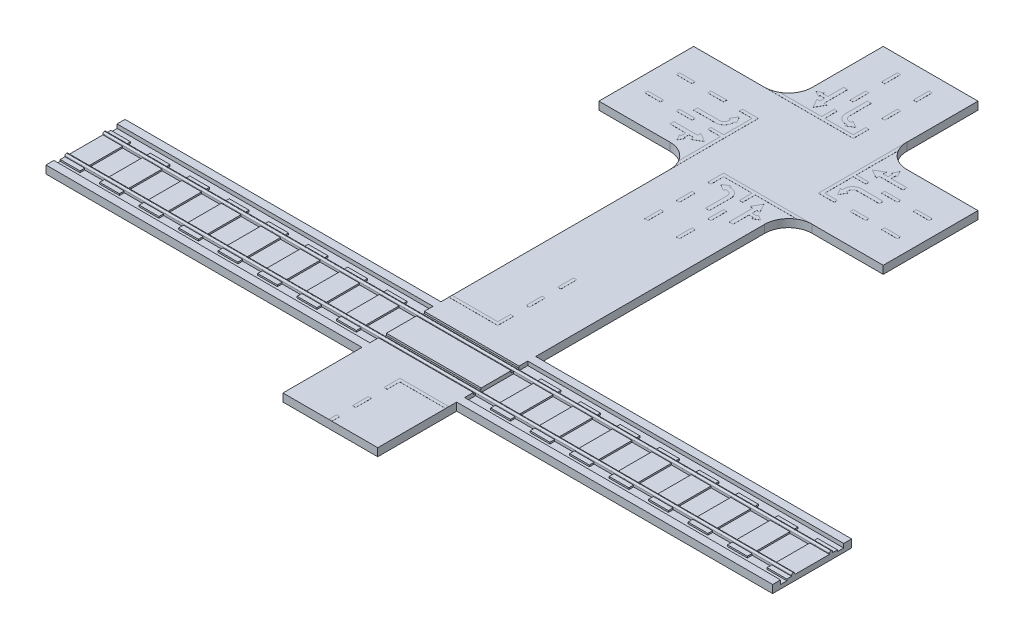
SolidWorks part; units mm, degrees
ref_plane "Front Plane" through (0, 0, 0) normal (0, 0, 1) x (1, 0, 0)
ref_plane "Top Plane" through (0, 0, 0) normal (0, 1, 0) x (1, 0, 0)
ref_plane "Right Plane" through (0, 0, 0) normal (1, 0, 0) x (0, 0, -1)
sketch "Skizze1" plane through (0, 0, 0) normal (0, 1, 0) x (1, 0, 0)
  line L1 (-60, 0) -> (-120, 0)
  line L2 (0, 60) -> (0, 120)
  line L3 (-60, 180) -> (-120, 180)
  line L4 (-180, 60) -> (-180, 120)
  line L7 (-180, 120) -> (-120, 120)
  line L8 (-120, 180) -> (-120, 120)
  line L11 (0, 120) -> (-60, 120)
  line L12 (-60, 180) -> (-60, 120)
  line L15 (0, 60) -> (-60, 60)
  line L16 (-60, 0) -> (-60, 60)
  line L19 (-180, 60) -> (-120, 60)
  line L20 (-120, 0) -> (-120, 60)
  dimension "D3" = 60
  dimension "D4" = 60
  dimension "D5" = 60
  dimension "D6" = 60
  dimension "D7" = 60
  dimension "D8" = 60
  dimension "D9" = 60
  dimension "D10" = 60
extrude "Aufsatz-Linear austragen1" add sketch "Skizze1" along normal blind 5
fillet "Verrundung1" radius 15 4 edges at (-60, 2.5, -120) (-60, 2.5, -60) (-120, 2.5, -60) (-120, 2.5, -120)
sketch "Skizze2" plane through (0, 5, 0) normal (0, 1, 0) x (1, 0, 0)
  line L1 (-101, 60) -> (-99, 60)
  line L2 (-101, 60) -> (-101, 50)
  line L3 (-101, 50) -> (-99, 50)
  line L4 (-99, 60) -> (-99, 50)
  line L5 (-101, 40) -> (-99, 40)
  line L6 (-101, 40) -> (-101, 30)
  line L7 (-101, 30) -> (-99, 30)
  line L8 (-99, 40) -> (-99, 30)
  line L9 (-101, 20) -> (-99, 20)
  line L10 (-101, 20) -> (-101, 10)
  line L11 (-101, 10) -> (-99, 10)
  line L12 (-99, 20) -> (-99, 10)
  line L13 (-120, 0) -> (-60, 0) construction
  line L21 (-120, 45) -> (-120, 0) construction
  line L22 (-81, 20) -> (-81, 10)
  line L23 (-79, 10) -> (-81, 10)
  line L24 (-79, 20) -> (-79, 10)
  line L25 (-79, 20) -> (-81, 20)
  line L26 (-81, 40) -> (-81, 30)
  line L27 (-79, 30) -> (-81, 30)
  line L28 (-79, 40) -> (-79, 30)
  line L29 (-79, 40) -> (-81, 40)
  line L30 (-81, 60) -> (-81, 50)
  line L31 (-79, 50) -> (-81, 50)
  line L32 (-79, 60) -> (-79, 50)
  line L33 (-79, 60) -> (-81, 60)
  line L34 (-60, 79) -> (-60, 81)
  line L35 (-60, 79) -> (-50, 79)
  line L36 (-50, 79) -> (-50, 81)
  line L37 (-60, 81) -> (-50, 81)
  line L38 (-40, 79) -> (-40, 81)
  line L39 (-40, 79) -> (-30, 79)
  line L40 (-30, 79) -> (-30, 81)
  line L41 (-40, 81) -> (-30, 81)
  line L42 (-20, 79) -> (-20, 81)
  line L43 (-20, 79) -> (-10, 79)
  line L44 (-10, 79) -> (-10, 81)
  line L45 (-20, 81) -> (-10, 81)
  line L46 (-20, 99) -> (-10, 99)
  line L47 (-10, 101) -> (-10, 99)
  line L48 (-20, 101) -> (-10, 101)
  line L49 (-20, 101) -> (-20, 99)
  line L50 (-40, 99) -> (-30, 99)
  line L51 (-30, 101) -> (-30, 99)
  line L52 (-40, 101) -> (-30, 101)
  line L53 (-40, 101) -> (-40, 99)
  line L54 (-60, 99) -> (-50, 99)
  line L55 (-50, 101) -> (-50, 99)
  line L56 (-60, 101) -> (-50, 101)
  line L57 (-60, 101) -> (-60, 99)
  line L58 (-120, 101) -> (-120, 99)
  line L59 (-120, 101) -> (-130, 101)
  line L60 (-130, 101) -> (-130, 99)
  line L61 (-120, 99) -> (-130, 99)
  line L62 (-140, 101) -> (-140, 99)
  line L63 (-140, 101) -> (-150, 101)
  line L64 (-150, 101) -> (-150, 99)
  line L65 (-140, 99) -> (-150, 99)
  line L66 (-160, 101) -> (-160, 99)
  line L67 (-160, 101) -> (-170, 101)
  line L68 (-170, 101) -> (-170, 99)
  line L69 (-160, 99) -> (-170, 99)
  line L70 (-160, 81) -> (-170, 81)
  line L71 (-170, 79) -> (-170, 81)
  line L72 (-160, 79) -> (-170, 79)
  line L73 (-160, 79) -> (-160, 81)
  line L74 (-140, 81) -> (-150, 81)
  line L75 (-150, 79) -> (-150, 81)
  line L76 (-140, 79) -> (-150, 79)
  line L77 (-140, 79) -> (-140, 81)
  line L78 (-120, 81) -> (-130, 81)
  line L79 (-130, 79) -> (-130, 81)
  line L80 (-120, 79) -> (-130, 79)
  line L81 (-120, 79) -> (-120, 81)
  line L82 (-79, 120) -> (-81, 120)
  line L83 (-79, 120) -> (-79, 130)
  line L84 (-79, 130) -> (-81, 130)
  line L85 (-81, 120) -> (-81, 130)
  line L86 (-79, 140) -> (-81, 140)
  line L87 (-79, 140) -> (-79, 150)
  line L88 (-79, 150) -> (-81, 150)
  line L89 (-81, 140) -> (-81, 150)
  line L90 (-79, 160) -> (-81, 160)
  line L91 (-79, 160) -> (-79, 170)
  line L92 (-79, 170) -> (-81, 170)
  line L93 (-81, 160) -> (-81, 170)
  line L94 (-99, 160) -> (-99, 170)
  line L95 (-101, 170) -> (-99, 170)
  line L96 (-101, 160) -> (-101, 170)
  line L97 (-101, 160) -> (-99, 160)
  line L98 (-99, 140) -> (-99, 150)
  line L99 (-101, 150) -> (-99, 150)
  line L100 (-101, 140) -> (-101, 150)
  line L101 (-101, 140) -> (-99, 140)
  line L102 (-99, 120) -> (-99, 130)
  line L103 (-101, 130) -> (-99, 130)
  line L104 (-101, 120) -> (-101, 130)
  line L105 (-101, 120) -> (-99, 120)
  dimension "D1" = 2
  dimension "D2" = 2
  dimension "D3" = 2
  dimension "D4" = 10
  dimension "D5" = 10
  dimension "D6" = 10
  dimension "D7" = 10
  dimension "D8" = 10
  dimension "D9" = 10
  dimension "D10" = 19
  dimension "D11" = 19
  dimension "D12" = 19
extrude "Aufsatz-Linear austragen2" add sketch "Skizze2" along normal blind 0.05
sketch "Skizze3" plane through (0, 5, 0) normal (0, 1, 0) x (1, 0, 0)
  line L0 (-72.5, 35) -> (-70, 35)
  line L1 (-70, 35) -> (-70, 45)
  line L2 (-70, 50) -> (-68, 50)
  line L3 (-68, 50) -> (-71.25, 55.6292)
  line L4 (-71.25, 55.6292) -> (-74.5, 50)
  line L5 (-74.5, 50) -> (-72.5, 50)
  line L6 (-72.5, 50) -> (-72.5, 35)
  line L7 (-120, 0) -> (-60, 0) construction
  line L8 (-60, 0) -> (-60, 45) construction
  line L9 (-70, 45) -> (-67, 45)
  line L10 (-67, 45) -> (-67, 44)
  line L11 (-67, 44) -> (-63.5359, 46)
  line L12 (-63.5359, 46) -> (-67, 48)
  line L13 (-67, 48) -> (-67, 47)
  line L14 (-67, 47) -> (-70, 47)
  line L15 (-70, 47) -> (-70, 50)
  line L16 (-81, 58) -> (-52.4833, 58)
  line L17 (-81, 60) -> (-41, 60)
  line L18 (-81, 60) -> (-81, 58)
  line L19 (-81, 58) -> (-52.4833, 58)
  arc A0 (-45, 60) -> (-60, 45) centre (-45, 45) ccw construction
  arc A2 (-45, 60) -> (-52.4833, 58) centre (-45, 45) ccw
  dimension "D1" = 2.5
  dimension "D2" = 1.25
  dimension "D3" = 15
  dimension "D4" = 2
  dimension "D5" = 60
  dimension "D6" = 60
  dimension "D7" = 15
  dimension "D8" = 35
  dimension "D9" = 10
  dimension "D10" = 2
  dimension "D11" = 60
  dimension "D12" = 60
  dimension "D13" = 1
  dimension "D14" = 3
  dimension "D15" = 10
  dimension "D16" = 1
  dimension "D17" = 1
extrude "Aufsatz-Linear austragen8" add sketch "Skizze3" along normal blind 0.05 contours A2 L17 L18 L16 | L14 L15 L2 L3 L4 L5 L6 L0 L1 L9 L10 L11 L12 L13 region at (-70.465, 5, -45.6545) region at (-65.4801, 5, -59.0319)
sketch "Skizze4" plane through (0, 5, 0) normal (0, 1, 0) x (1, 0, 0)
  line L0 (-85, 48.63) -> (-85, 35)
  line L1 (-101, 60) -> (-79, 60)
  line L2 (-101, 60) -> (-101, 58)
  line L3 (-101, 58) -> (-79, 58)
  line L4 (-79, 60) -> (-79, 58)
  line L5 (-85, 35) -> (-87.5, 35)
  line L6 (-87.5, 48.63) -> (-87.5, 35)
  line L7 (-90.5, 51.63) -> (-91.5, 51.63)
  line L8 (-91.5, 51.63) -> (-91.5, 50.38)
  line L9 (-91.5, 50.38) -> (-95.8301, 52.88)
  line L10 (-95.8301, 52.88) -> (-91.5, 55.38)
  line L11 (-91.5, 55.38) -> (-91.5, 54.13)
  line L12 (-90.5, 54.13) -> (-91.5, 54.13)
  line L13 (-120, 0) -> (-60, 0) construction
  line L15 (-81, 60) -> (-81, 50) construction
  line L71 (-101, 60) -> (-101, 58)
  line L72 (-79, 58) -> (-101, 58)
  line L73 (-79, 60) -> (-79, 58)
  line L74 (-79, 60) -> (-101, 60)
  arc A0 (-85, 48.63) -> (-90.5, 54.13) centre (-90.5, 48.63) ccw
  arc A1 (-87.5, 48.63) -> (-90.5, 51.63) centre (-90.5, 48.63) ccw
  dimension "D1" = 2.5
  dimension "D2" = 11
  dimension "D13" = 1
  dimension "D14" = 13.63
  dimension "D12" = 3
  dimension "D3" = 1.25
  dimension "D4" = 1.25
  dimension "D5" = 1.25
  dimension "D6" = 60
  dimension "D7" = 60
  dimension "D8" = 48.63
  dimension "D9" = 0
  dimension "D10" = 35
  dimension "D11" = 9.5
extrude "Aufsatz-Linear austragen13" add sketch "Skizze4" along normal blind 0.05 contours A1 L6 L5 L0 A0 L12 L11 L10 L9 L8 L7 | L4 L1 L2 L3 region at (-85.2308, 5, -41.815) region at (-90, 5, -59)
sketch "Skizze8" plane through (0, 5, 0) normal (0, 1, 0) x (1, 0, 0)
  line L0 (-60, 79) -> (-60, 135)
  line L1 (-60, 135) -> (-60, 79)
  line L2 (-58, 79) -> (-58, 127.5167)
  line L3 (-60, 79) -> (-50, 79) construction
  line L4 (-79, 120) -> (-135, 120)
  line L6 (-135, 120) -> (-79, 120)
  line L7 (-60, 135) -> (-58, 127.5167)
  line L8 (-79, 122) -> (-122, 122)
  line L9 (-79, 120) -> (-79, 130) construction
  line L10 (-79, 122) -> (-79, 120)
  line L11 (-120, 101) -> (-122, 101)
  line L12 (-58, 79) -> (-60, 79)
  line L13 (-108.737, 124.3934) -> (-108.763, 124.3934)
  line L14 (-35, 107.5) -> (-50, 107.5)
  line L15 (-50, 107.5) -> (-50, 105.5)
  line L16 (-50, 105.5) -> (-55.6292, 108.75)
  line L17 (-55.6292, 108.75) -> (-50, 112)
  line L18 (-50, 112) -> (-50, 110)
  line L19 (-50, 110) -> (-47, 110)
  line L20 (-47, 110) -> (-47, 113)
  line L21 (-47, 113) -> (-48, 113)
  line L22 (-48, 113) -> (-46, 116.4641)
  line L23 (-46, 116.4641) -> (-44, 113)
  line L24 (-44, 113) -> (-45, 113)
  line L25 (-45, 113) -> (-45, 110)
  line L26 (-45, 110) -> (-35, 110)
  line L27 (-35, 110) -> (-35, 107.5)
  line L28 (-48.8792, 95) -> (-35, 95)
  line L29 (-35, 95) -> (-35, 92.5)
  line L30 (-35, 92.5) -> (-48.8792, 92.5)
  line L31 (-51.8792, 89.5) -> (-51.8792, 88.5)
  line L32 (-51.8792, 88.5) -> (-50.6292, 88.5)
  line L33 (-50.6292, 88.5) -> (-53.1292, 84.1699)
  line L34 (-53.1292, 84.1699) -> (-55.6292, 88.5)
  line L35 (-55.6292, 88.5) -> (-54.3792, 88.5)
  line L36 (-54.3792, 88.5) -> (-54.3792, 89.5)
  line L37 (-60, 99) -> (-50, 99) construction
  line L38 (0, 60) -> (0, 120) construction
  line L39 (0, 120) -> (-45, 120) construction
  line L40 (-180, 120) -> (-180, 60) construction
  line L41 (-180, 60) -> (-135, 60) construction
  line L42 (-120, 45) -> (-122, 52.4833)
  line L43 (-135, 120) -> (-127.5167, 122)
  line L44 (-79, 122) -> (-79, 120)
  line L51 (-88.4609, 124.3934) -> (-88.5, 124.3934)
  line L53 (-122, 122) -> (-127.5167, 122)
  line L76 (-79, 120) -> (-135, 120)
  line L77 (-135, 120) -> (-79, 120)
  line L78 (-79, 122) -> (-122, 122)
  line L79 (-107.5, 145) -> (-107.5, 130)
  line L80 (-107.5, 130) -> (-105.5, 130)
  line L81 (-105.5, 130) -> (-108.75, 124.3708)
  line L82 (-108.75, 124.3708) -> (-112, 130)
  line L83 (-112, 130) -> (-110, 130)
  line L84 (-110, 130) -> (-110, 133)
  line L85 (-110, 133) -> (-113, 133)
  line L86 (-113, 133) -> (-113, 132)
  line L87 (-113, 132) -> (-116.4641, 134)
  line L88 (-116.4641, 134) -> (-113, 136)
  line L89 (-113, 136) -> (-113, 135)
  line L90 (-113, 135) -> (-110, 135)
  line L91 (-110, 135) -> (-110, 145)
  line L92 (-110, 145) -> (-107.5, 145)
  line L93 (-95, 131.1208) -> (-95, 145)
  line L94 (-95, 145) -> (-92.5, 145)
  line L95 (-92.5, 145) -> (-92.5, 131.1208)
  line L96 (-89.5, 128.1208) -> (-88.5, 128.1208)
  line L97 (-88.5, 128.1208) -> (-88.5, 129.3708)
  line L98 (-88.5, 129.3708) -> (-84.1699, 126.8708)
  line L99 (-84.1699, 126.8708) -> (-88.5, 124.3708)
  line L100 (-88.5, 124.3708) -> (-88.5, 125.6208)
  line L101 (-88.5, 125.6208) -> (-89.5, 125.6208)
  line L104 (-120, 101) -> (-120, 45)
  line L105 (-120, 45) -> (-120, 101)
  line L106 (-122, 101) -> (-122, 52.4833)
  line L107 (-145, 72.5) -> (-130, 72.5)
  line L108 (-130, 72.5) -> (-130, 74.5)
  line L109 (-130, 74.5) -> (-124.3708, 71.25)
  line L110 (-124.3708, 71.25) -> (-130, 68)
  line L111 (-130, 68) -> (-130, 70)
  line L112 (-130, 70) -> (-133, 70)
  line L113 (-133, 70) -> (-133, 67)
  line L114 (-133, 67) -> (-132, 67)
  line L115 (-132, 67) -> (-134, 63.5359)
  line L116 (-134, 63.5359) -> (-136, 67)
  line L117 (-136, 67) -> (-135, 67)
  line L118 (-135, 67) -> (-135, 70)
  line L119 (-135, 70) -> (-145, 70)
  line L120 (-145, 70) -> (-145, 72.5)
  line L121 (-131.1208, 85) -> (-145, 85)
  line L122 (-145, 85) -> (-145, 87.5)
  line L123 (-145, 87.5) -> (-131.1208, 87.5)
  line L124 (-128.1208, 90.5) -> (-128.1208, 91.5)
  line L125 (-128.1208, 91.5) -> (-129.3708, 91.5)
  line L126 (-129.3708, 91.5) -> (-126.8708, 95.8301)
  line L127 (-126.8708, 95.8301) -> (-124.3708, 91.5)
  line L128 (-124.3708, 91.5) -> (-125.6208, 91.5)
  line L129 (-125.6208, 91.5) -> (-125.6208, 90.5)
  arc A0 (-60, 135) -> (-45, 120) centre (-45, 135) ccw construction
  arc A2 (-48.8792, 92.5) -> (-51.8792, 89.5) centre (-48.8792, 89.5) ccw
  arc A3 (-48.8792, 95) -> (-54.3792, 89.5) centre (-48.8792, 89.5) ccw
  arc A4 (-135, 120) -> (-120, 135) centre (-135, 135) ccw construction
  arc A6 (-120, 45) -> (-122, 52.4833) centre (-135, 45) ccw
  arc A7 (-92.5, 131.1208) -> (-89.5, 128.1208) centre (-89.5, 131.1208) ccw
  arc A8 (-95, 131.1208) -> (-89.5, 125.6208) centre (-89.5, 131.1208) ccw
  arc A9 (-131.1208, 87.5) -> (-128.1208, 90.5) centre (-131.1208, 90.5) ccw
  arc A10 (-131.1208, 85) -> (-125.6208, 90.5) centre (-131.1208, 90.5) ccw
  arc A11 (-58, 127.5167) -> (-60, 135) centre (-45, 135) cw
  arc A14 (-127.5167, 122) -> (-135, 120) centre (-135, 135) cw
  dimension "D5" = 3
  dimension "D6" = 5.5
  dimension "D1" = 2
  dimension "D3" = 2
  dimension "D4" = 2.5
  dimension "D7" = 1
  dimension "D8" = 1.25
  dimension "D9" = 1.25
  dimension "D10" = 60
  dimension "D11" = 60
  dimension "D12" = 9.5
  dimension "D13" = 35
  dimension "D14" = 35
  dimension "D15" = 3
  dimension "D16" = 15
  dimension "D17" = 1
  dimension "D18" = 1
  dimension "D19" = 10
  dimension "D20" = 2
  dimension "D21" = 2.5
  dimension "D22" = 2
  dimension "D23" = 2
  dimension "D24" = 60
  dimension "D25" = 60
  dimension "D26" = 60
  dimension "D27" = 60
  dimension "D28" = 3
  dimension "D29" = 10
  dimension "D30" = 5.6292
  dimension "D31" = 0
  dimension "D32" = 2.5
  dimension "D33" = 4.3301
  dimension "D34" = 2
  dimension "D35" = 35
  dimension "D36" = 2.5
  dimension "D37" = 2
  dimension "D38" = 2
  dimension "D39" = 3
  dimension "D40" = 10
  dimension "D41" = 15
  dimension "D42" = 1
  dimension "D43" = 1
  dimension "D44" = 60
  dimension "D45" = 60
  dimension "D46" = 10
  dimension "D47" = 2
  dimension "D48" = 10
  dimension "D49" = 5
  dimension "D50" = 60
  dimension "D51" = 60
  dimension "D52" = 3
  dimension "D53" = 3
  dimension "D54" = 5.6292
  dimension "D55" = 58
extrude "Aufsatz-Linear austragen14" add sketch "Skizze8" along normal blind 0.05 contours L92 L91 L90 L89 L88 L87 L86 L85 L84 L83 L82 L13 L81 L80 L79 | L53 A14 L4 L10 L8 | L93 A8 L101 L100 L51 L99 L98 L97 L96 A7 L95 L94 | L27 L26 L25 L24 L23 L22 L21 L20 L19 L18 L17 L16 L15 L14 | L2 A11 L0 L12 | L28 A3 L36 L35 L34 L33 L32 L31 A2 L30 L29 | A6 L104 L11 L106 | L121 A10 L129 L128 L127 L126 L125 L124 A9 L123 L122 | L120 L119 L118 L117 L116 L115 L114 L113 L112 L111 L110 L109 L108 L107 region at (-59.0194, 5, -104.5004) region at (-104.5004, 5, -120.9806) region at (-120.9806, 5, -75.4996) region at (-109.535, 5, -134.3455) region at (-45.6545, 5, -109.535) region at (-41.9396, 5, -94.767) region at (-88.4805, 5, -124.6262) region at (-134.3455, 5, -70.465) region at (-138.0604, 5, -85.233)
sketch "Skizze9" plane through (0, 5, 0) normal (0, 1, 0) x (1, 0, 0)
  line L0 (-60, 0) -> (-120, 0)
  line L1 (-320, -100) -> (-320, -150)
  line L2 (-120, -150) -> (-120, -200)
  line L3 (140, -150) -> (140, -100)
  line L4 (-120, -200) -> (-60, -200)
  line L5 (-60, 0) -> (-60, -100)
  line L6 (-60, -100) -> (140, -100)
  line L7 (140, -100) -> (140, -150)
  line L8 (140, -150) -> (-60, -150)
  line L9 (-320, -150) -> (-320, -100)
  line L10 (-320, -100) -> (-120, -100)
  line L11 (-120, 0) -> (-120, -100)
  line L12 (-60, -200) -> (-60, -150)
  line L13 (-120, -150) -> (-320, -150)
  dimension "D1" = 100
  dimension "D2" = 50
  dimension "D3" = 50
  dimension "D4" = 50
  dimension "D5" = 200
  dimension "D6" = 200
extrude "Aufsatz-Linear austragen15" add sketch "Skizze9" against normal blind 5 contours L13 L2 L4 L12 L8 L3 L6 L5 L0 L11 L10 L1 region at (-90, 5, 115.625)
sketch "Skizze10" plane through (0, 5, 0) normal (0, 1, 0) x (1, 0, 0)
  line L1 (-89, -200) -> (-91, -200)
  line L2 (-89, -200) -> (-89, -195)
  line L3 (-89, -195) -> (-91, -195)
  line L4 (-91, -200) -> (-91, -195)
  line L5 (-89, -185) -> (-91, -185)
  line L6 (-89, -185) -> (-89, -175)
  line L7 (-89, -175) -> (-91, -175)
  line L8 (-91, -185) -> (-91, -175)
  line L9 (-89, -165) -> (-91, -165)
  line L10 (-89, -165) -> (-89, -155)
  line L11 (-89, -155) -> (-91, -155)
  line L12 (-91, -165) -> (-91, -155)
  line L13 (-91, -155) -> (-91, -157)
  line L15 (-60, -155) -> (-91, -155)
  line L16 (-91, -157) -> (-60, -157)
  line L17 (-120, -200) -> (-60, -200) construction
  line L18 (-60, -200) -> (-60, -150) construction
  line L19 (-60, -157) -> (-60, -155)
  dimension "D1" = 2
  dimension "D2" = 2
  dimension "D3" = 2
  dimension "D4" = 10
  dimension "D5" = 5
  dimension "D6" = 10
  dimension "D7" = 0
  dimension "D8" = 10
  dimension "D9" = 10
  dimension "D10" = 29
  dimension "D11" = 29
  dimension "D12" = 29
  dimension "D13" = 2
  dimension "D14" = 0
extrude "Aufsatz-Linear austragen17" add sketch "Skizze10" along normal blind 0.05 contours L16 L19 L15 L10 | L12 L16 L10 L11 | L16 L12 L9 L10 | L8 L5 L6 L7 | L4 L1 L2 L3 region at (-90, 5, 197.5) region at (-90, 5, 180) region at (-90, 5, 161) region at (-90, 5, 156) region at (-74.5, 5, 156)
sketch "Skizze11" plane through (0, 5, 0) normal (0, 1, 0) x (1, 0, 0)
  line L0 (-320, -100) -> (-120, -100) construction
  line L1 (-120, 45) -> (-120, -100) construction
  line L2 (-120, -95) -> (-89, -95)
  line L3 (-89, -95) -> (-89, -85)
  line L4 (-89, -85) -> (-91, -85)
  line L5 (-91, -85) -> (-91, -93)
  line L6 (-91, -93) -> (-120, -93)
  line L7 (-120, -93) -> (-120, -95)
  line L9 (-89, -75) -> (-91, -75)
  line L10 (-89, -75) -> (-89, -65)
  line L11 (-89, -65) -> (-91, -65)
  line L12 (-91, -75) -> (-91, -65)
  line L13 (-89, -55) -> (-91, -55)
  line L14 (-89, -55) -> (-89, -45)
  line L15 (-89, -45) -> (-91, -45)
  line L16 (-91, -55) -> (-91, -45)
  dimension "D1" = 2
  dimension "D2" = 31
  dimension "D3" = 29
  dimension "D4" = 5
  dimension "D5" = 10
  dimension "D6" = 10
  dimension "D7" = 10
  dimension "D8" = 10
  dimension "D9" = 10
  dimension "D10" = 29
  dimension "D11" = 29
  dimension "D12" = 2
  dimension "D13" = 2
extrude "Aufsatz-Linear austragen18" add sketch "Skizze11" along normal blind 0.05
sketch "Skizze12" plane through (0, 5, 0) normal (0, 1, 0) x (1, 0, 0)
  line L0 (-320, -100) -> (-320, -150) construction
  line L1 (-320, -145) -> (-120, -145)
  line L2 (-320, -145) -> (-320, -105)
  line L3 (-320, -105) -> (-120, -105)
  line L4 (-120, -145) -> (-120, -105)
  line L5 (140, -150) -> (140, -100) construction
  line L6 (140, -145) -> (-60, -145)
  line L7 (140, -145) -> (140, -105)
  line L8 (140, -105) -> (-60, -105)
  line L9 (-60, -145) -> (-60, -105)
  line L10 (140, -150) -> (-60, -150) construction
  line L11 (-120, -150) -> (-320, -150) construction
  dimension "D1" = 40
  dimension "D2" = 5
  dimension "D3" = 40
  dimension "D4" = 5
  dimension "D5" = 200
  dimension "D6" = 200
extrude "Schnitt-Linear austragen1" cut sketch "Skizze12" against normal blind 2.5
sketch "Skizze16" plane through (0, 2.5, 0) normal (0, 1, 0) x (1, 0, 0)
  line L0 (-120, -145) -> (-120, -105) construction
  line L1 (-120, -112) -> (-320, -112)
  line L2 (-120, -112) -> (-120, -114)
  line L3 (-120, -114) -> (-320, -114)
  line L4 (-320, -112) -> (-320, -114)
  line L5 (-320, -105) -> (-320, -145) construction
  line L6 (140, -145) -> (140, -105) construction
  line L7 (-120, -136) -> (-320, -136)
  line L8 (-120, -136) -> (-120, -138)
  line L9 (-120, -138) -> (-320, -138)
  line L10 (-320, -136) -> (-320, -138)
  line L15 (140, -114) -> (-60, -114)
  line L16 (140, -114) -> (140, -112)
  line L17 (140, -112) -> (-60, -112)
  line L18 (-60, -114) -> (-60, -112)
  line L19 (-60, -105) -> (-60, -145) construction
  line L20 (-60, -145) -> (140, -145) construction
  line L21 (-60, -136) -> (140, -136)
  line L22 (-60, -136) -> (-60, -138)
  line L23 (-60, -138) -> (140, -138)
  line L24 (140, -136) -> (140, -138)
  line L26 (140, -105) -> (-60, -105) construction
  line L27 (-120, -105) -> (-320, -105) construction
  line L28 (-320, -145) -> (-120, -145) construction
  dimension "D1" = 2
  dimension "D2" = 2
  dimension "D3" = 22
  dimension "D4" = 7
  dimension "D5" = 7
  dimension "D6" = 7
  dimension "D7" = 2
  dimension "D8" = 2
  dimension "D9" = 7
  dimension "D10" = 200
extrude "Aufsatz-Linear austragen20" add sketch "Skizze16" along normal blind 2.5
sketch "Skizze17" plane through (0, 5, 0) normal (0, 1, 0) x (1, 0, 0)
  line L0 (-60, -105) -> (-60, -112) construction
  line L1 (-120, -112) -> (-60, -112)
  line L2 (-120, -112) -> (-120, -110.5)
  line L3 (-120, -110.5) -> (-60, -110.5)
  line L4 (-60, -112) -> (-60, -110.5)
  line L5 (-120, -136) -> (-120, -114) construction
  line L6 (-60, -114) -> (-120, -114)
  line L7 (-60, -114) -> (-60, -115.5)
  line L8 (-60, -115.5) -> (-120, -115.5)
  line L9 (-120, -114) -> (-120, -115.5)
  line L10 (-60, -114) -> (-60, -136) construction
  line L11 (-120, -136) -> (-60, -136)
  line L12 (-120, -136) -> (-120, -134.5)
  line L13 (-120, -134.5) -> (-60, -134.5)
  line L14 (-60, -136) -> (-60, -134.5)
  line L15 (-120, -145) -> (-120, -138) construction
  line L16 (-60, -138) -> (-120, -138)
  line L17 (-60, -138) -> (-60, -139.5)
  line L18 (-60, -139.5) -> (-120, -139.5)
  line L19 (-120, -138) -> (-120, -139.5)
  dimension "D1" = 1.5
  dimension "D2" = 1.5
  dimension "D3" = 1.5
  dimension "D4" = 1.5
extrude "Schnitt-Linear austragen3" cut sketch "Skizze17" against normal blind 1.25
sketch "Skizze18" plane through (0, 2.5, 0) normal (0, 1, 0) x (1, 0, 0)
  line L0 (140, -105) -> (-60, -105) construction
  line L1 (-245, -109) -> (-232.5, -109)
  line L2 (-245, -109) -> (-245, -141)
  line L3 (-245, -141) -> (-232.5, -141)
  line L4 (-232.5, -109) -> (-232.5, -141)
  line L5 (-220, -109) -> (-207.5, -109)
  line L6 (-220, -109) -> (-220, -141)
  line L7 (-220, -141) -> (-207.5, -141)
  line L8 (-207.5, -109) -> (-207.5, -141)
  line L9 (-195, -109) -> (-182.5, -109)
  line L10 (-195, -109) -> (-195, -141)
  line L11 (-195, -141) -> (-182.5, -141)
  line L12 (-182.5, -109) -> (-182.5, -141)
  line L13 (-170, -109) -> (-157.5, -109)
  line L14 (-170, -109) -> (-170, -141)
  line L15 (-170, -141) -> (-157.5, -141)
  line L16 (-157.5, -109) -> (-157.5, -141)
  line L17 (-145, -141) -> (-132.5, -141)
  line L18 (-145, -141) -> (-145, -109)
  line L19 (-145, -109) -> (-132.5, -109)
  line L20 (-132.5, -141) -> (-132.5, -109)
  line L21 (-120, -136) -> (-120, -114) construction
  line L22 (-120, -105) -> (-320, -105) construction
  line L23 (-120, -105) -> (-320, -105) construction
  line L24 (-320, -145) -> (-120, -145) construction
  line L26 (-60, -114) -> (-60, -136) construction
  line L27 (140, -112) -> (140, -105) construction
  line L28 (77.5, -109) -> (90, -109)
  line L29 (65, -109) -> (52.5, -109)
  line L30 (65, -109) -> (65, -141)
  line L31 (65, -141) -> (52.5, -141)
  line L32 (52.5, -109) -> (52.5, -141)
  line L33 (40, -109) -> (27.5, -109)
  line L34 (40, -109) -> (40, -141)
  line L35 (40, -141) -> (27.5, -141)
  line L36 (27.5, -109) -> (27.5, -141)
  line L37 (15, -109) -> (2.5, -109)
  line L38 (15, -109) -> (15, -141)
  line L39 (15, -141) -> (2.5, -141)
  line L40 (2.5, -109) -> (2.5, -141)
  line L41 (-10, -109) -> (-22.5, -109)
  line L42 (-10, -109) -> (-10, -141)
  line L43 (-10, -141) -> (-22.5, -141)
  line L44 (-22.5, -109) -> (-22.5, -141)
  line L45 (-35, -109) -> (-47.5, -109)
  line L46 (-35, -109) -> (-35, -141)
  line L47 (-35, -141) -> (-47.5, -141)
  line L48 (-47.5, -109) -> (-47.5, -141)
  line L49 (140, -105) -> (-60, -105) construction
  line L50 (140, -109) -> (127.5, -109)
  line L51 (-60, -145) -> (140, -145) construction
  line L52 (140, -109) -> (140, -141)
  line L53 (-60, -145) -> (140, -145) construction
  line L54 (77.5, -109) -> (77.5, -141)
  line L55 (77.5, -141) -> (90, -141)
  line L56 (90, -109) -> (90, -141)
  line L57 (115, -141) -> (102.5, -141)
  line L58 (115, -141) -> (115, -109)
  line L59 (115, -109) -> (102.5, -109)
  line L60 (102.5, -141) -> (102.5, -109)
  line L61 (140, -141) -> (127.5, -141)
  line L62 (127.5, -109) -> (127.5, -141)
  line L64 (-257.5, -109) -> (-270, -109)
  line L65 (-257.5, -109) -> (-257.5, -141)
  line L66 (-257.5, -141) -> (-270, -141)
  line L67 (-270, -109) -> (-270, -141)
  line L68 (-282.5, -109) -> (-295, -109)
  line L69 (-282.5, -109) -> (-282.5, -141)
  line L70 (-282.5, -141) -> (-295, -141)
  line L71 (-295, -109) -> (-295, -141)
  line L72 (-307.5, -109) -> (-320, -109)
  line L73 (-307.5, -109) -> (-307.5, -141)
  line L74 (-307.5, -141) -> (-320, -141)
  line L75 (-320, -109) -> (-320, -141)
  dimension "D2" = 4
  dimension "D3" = 12.5
  dimension "D4" = 4
  dimension "D5" = 12.5
  dimension "D6" = 12.5
  dimension "D7" = 4
  dimension "D8" = 12.5
  dimension "D9" = 12.5
  dimension "D10" = 4
  dimension "D11" = 12.5
  dimension "D12" = 12.5
  dimension "D13" = 12.5
  dimension "D14" = 12.5
  dimension "D15" = 4
  dimension "D16" = 4
  dimension "D17" = 4
  dimension "D18" = 4
  dimension "D19" = 4
  dimension "D20" = 12.5
  dimension "D21" = 12.5
  dimension "D22" = 4
  dimension "D23" = 12.5
  dimension "D24" = 12.5
  dimension "D25" = 12.5
  dimension "D26" = 12.5
  dimension "D27" = 12.5
  dimension "D28" = 12.5
  dimension "D29" = 12.5
  dimension "D30" = 12.5
  dimension "D31" = 4
  dimension "D32" = 4
  dimension "D33" = 4
  dimension "D34" = 4
  dimension "D35" = 4
  dimension "D36" = 4
  dimension "D37" = 4
  dimension "D38" = 4
  dimension "D39" = 4
  dimension "D40" = 4
  dimension "D41" = 12.5
  dimension "D42" = 12.5
  dimension "D43" = 12.5
  dimension "D44" = 12.5
  dimension "D45" = 12.5
  dimension "D46" = 32
  dimension "D47" = 4
  dimension "D48" = 4
  dimension "D49" = 4
  dimension "D50" = 12.5
  dimension "D51" = 4
  dimension "D52" = 32
  dimension "D53" = 12.5
  dimension "D54" = 12.5
  dimension "D55" = 12.5
  dimension "D56" = 12.5
  dimension "D57" = 12.5
  dimension "D58" = 12.5
  dimension "D59" = 32
  dimension "D60" = 32
  dimension "D61" = 32
  dimension "D62" = 4
  dimension "D63" = 4
  dimension "D64" = 4
extrude "Aufsatz-Linear austragen22" add sketch "Skizze18" along normal blind 1
fillet "Verrundung2" radius 1 4 edges at (-90, 5, 138) (-90, 5, 136) (-90, 5, 114) (-90, 5, 112)
fillet "Verrundung3" radius 0.25 4 edges at (-90, 3.75, 136) (-90, 3.75, 112) (-90, 3.75, 138) (-90, 3.75, 114)
